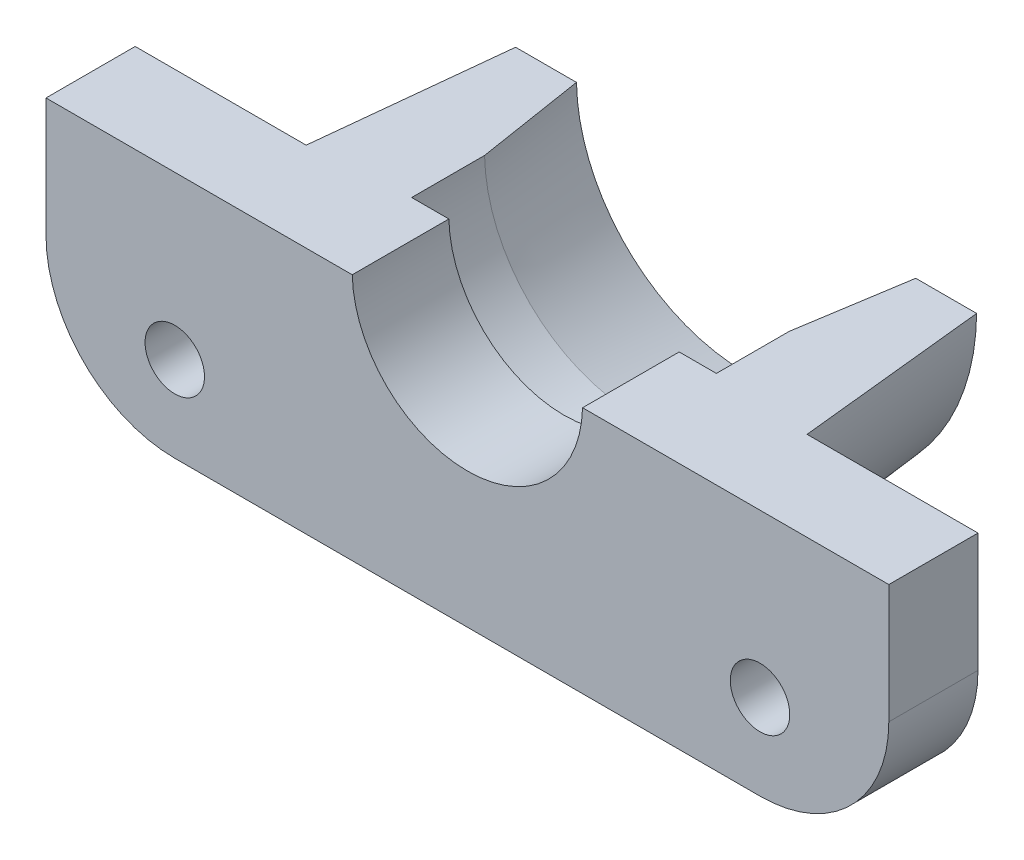
SolidWorks part; units mm, degrees
ref_plane "Front Plane" through (0, 0, 0) normal (0, 0, 1) x (1, 0, 0)
ref_plane "Top Plane" through (0, 0, 0) normal (0, 1, 0) x (1, 0, 0)
ref_plane "Right Plane" through (0, 0, 0) normal (1, 0, 0) x (0, 0, -1)
sketch "Sketch1" plane through (0, 0, 0) normal (0, 0, 1) x (1, 0, 0)
  line L0 (0, 0.15) -> (0, 13.6295) construction
  line L1 (0, 0.15) -> (13.4795, 0.15) construction
  line L2 (13.4787, 0) -> (-13.4787, 0) construction
  line L3 (13.4787, 0) -> (-13.4787, 0) construction
  line L4 (-22.6795, 0) -> (22.6795, 0)
  line L5 (22.6795, 0) -> (22.6795, -13.834)
  line L6 (22.6795, -13.834) -> (-22.6795, -13.834)
  line L7 (-22.6795, -13.834) -> (-22.6795, 0)
  line L9 (0, 13.6295) -> (0, 22.83) construction
  circle A0 centre (0, 0.15) radius 13.4795 construction
  arc A1 (-13.4787, 0) -> (13.4787, 0) centre (0, 0.15) ccw construction
  arc A2 (13.4787, 0) -> (-13.4787, 0) centre (0, 0.15) cw construction
  circle A3 centre (0, 0.15) radius 22.68 construction
sketch "Sketch2" plane through (0, 0, 0) normal (1, 0, 0) x (0, 0, -1)
  line L0 (14, 0.15) -> (-60.8, 0.15) construction
  line L1 (15, 0.15) -> (0, 0.15)
  line L2 (15, 0.15) -> (15, -8.9811)
  line L3 (15, -8.9811) -> (9.121, -8.05)
  line L4 (9.121, -8.05) -> (5.2, -8.05)
  line L5 (5.2, -8.05) -> (5.2, -6.05)
  line L6 (5.2, -6.05) -> (0, -6.05)
  line L7 (0, -6.05) -> (0, 0.15)
sketch "Sketch3" plane through (0, 0, 0) normal (1, 0, 0) x (0, 0, -1)
  line L0 (15, -12.2574) -> (0, -13.834) construction
  line L1 (4.8, -13.3295) -> (0, -13.3295)
  line L2 (0, -13.834) -> (0, 0) construction
  line L3 (0, 0) -> (15, 0)
  line L4 (15, 0) -> (15, -12.2574)
  line L5 (0, 0) -> (0, -13.3295)
  line L6 (15, -12.2574) -> (4.8, -13.3295)
extrude "Boss-Extrude2" add sketch "Sketch3" along normal up to surface (22.6795 mm away) and the other way up to surface (22.6795 mm away)
revolve "Cut-Revolve1" cut sketch "Sketch2" angle 360 about L1
sketch "Sketch4" plane through (0, 0.15, -14) normal (1, 0, 0) x (0, 0, -1)
  line L0 (1, 22.68) -> (1, 12.4074) construction
  line L1 (1, 12.4074) -> (-9.2, 13.4795)
  line L2 (1, 12.4074) -> (-66.304, 19.4814) construction
  line L3 (1, 9.1311) -> (1, 12.4074) construction
  line L4 (-9.2, 13.4795) -> (-9.2, 22.68) construction
  line L5 (1, 22.68) -> (-9.2, 22.68) construction
  line L6 (0, 0) -> (-74.8, 0) construction
  line L7 (0, 0) -> (-74.8, 0) construction
  line L8 (1, 12.4074) -> (1, 37.68)
  line L9 (1, 37.68) -> (-9.2, 37.68)
  line L10 (-9.2, 37.68) -> (-9.2, 13.4795)
  dimension "D1" = 15
revolve "Cut-Revolve2" cut sketch "Sketch4" angle 360 about L7
sketch "Sketch5" plane through (0, 0, -4.8) normal (0, 0, -1) x (-1, 0, 0)
  line L0 (-22.6795, -13.3295) -> (0, -13.3295) construction
  line L1 (0, 0) -> (0, -13.3295) construction
  line L2 (-22.6795, -13.3295) -> (-22.6795, -6.3987)
  line L3 (-22.6795, -13.3295) -> (-22.6795, 0) construction
  line L4 (-22.6795, -13.3295) -> (-15.7487, -13.3295)
  line L5 (22.6795, -13.3295) -> (22.6795, -6.3987)
  line L6 (22.6795, -13.3295) -> (15.7487, -13.3295)
  circle A0 centre (-15.7487, -8.7295) radius 1.6
  circle A1 centre (-15.7487, -8.7295) radius 4.6 construction
  arc A2 (-13.4787, 0) -> (0, -13.3295) centre (0, 0.15) ccw construction
  circle A3 centre (15.7487, -8.7295) radius 1.6
  arc A4 (-22.6795, -6.3987) -> (-15.7487, -13.3295) centre (-15.7487, -6.3987) ccw
  arc A5 (22.6795, -6.3987) -> (15.7487, -13.3295) centre (15.7487, -6.3987) cw
  dimension "D1" = 3.2
  dimension "D2" = 3
  dimension "D3" = 6.9308
extrude "Cut-Extrude1" cut sketch "Sketch5" against normal through all
